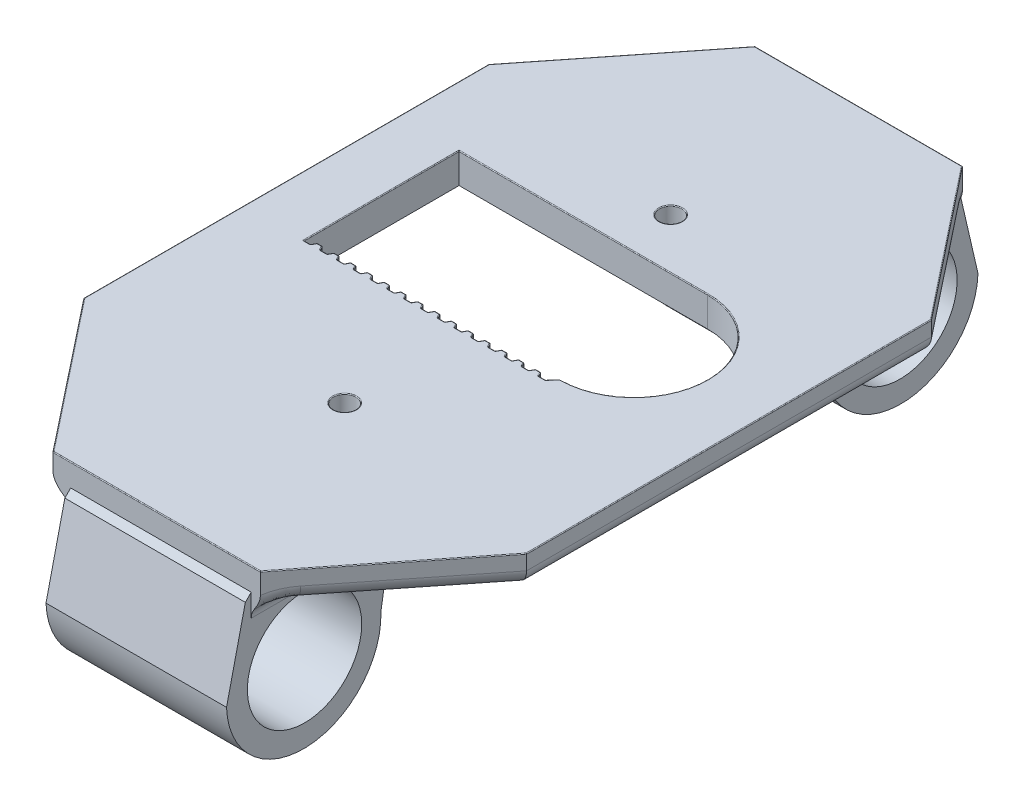
SolidWorks part; units mm, degrees
ref_plane "Front Plane" through (0, 0, 0) normal (0, 0, 1) x (1, 0, 0)
ref_plane "Top Plane" through (0, 0, 0) normal (0, 1, 0) x (1, 0, 0)
ref_plane "Right Plane" through (0, 0, 0) normal (1, 0, 0) x (0, 0, -1)
sketch "Sketch1" plane through (0, 0, 0) normal (0, 1, 0) x (1, 0, 0)
  line L0 (7.0479, -4.6463) -> (7.0479, 14.9632) construction
  line L1 (-25.9915, 14.9632) -> (-25.9915, -5.6662)
  line L2 (-25.9915, 4.6485) -> (16.8527, 5.1585) construction
  line L3 (-117.0016, -46.4316) -> (-117.0016, 46.6684) construction
  line L4 (-117.0016, 46.6684) -> (67.0292, 46.6684) construction
  line L5 (60, -47.6441) -> (-60, 47.3559) construction
  line L6 (60, 47.3559) -> (-60, -47.6441) construction
  line L7 (-25.9915, 14.9632) -> (7.0479, 14.9632)
  line L8 (-20.2659, -5.09) -> (-19.7122, -5.09)
  line L9 (-19.6107, -5.1507) -> (-19.3663, -5.6055)
  line L10 (-19.2648, -5.6662) -> (-18.4807, -5.6662)
  line L11 (-18.0333, -5.09) -> (-17.4796, -5.09)
  line L12 (-18.1348, -5.1507) -> (-18.3791, -5.6055)
  line L13 (-17.3781, -5.1507) -> (-17.1338, -5.6055)
  line L14 (-17.0322, -5.6662) -> (-16.2481, -5.6662)
  line L15 (-15.8007, -5.09) -> (-15.247, -5.09)
  line L16 (-15.9022, -5.1507) -> (-16.1466, -5.6055)
  line L17 (-15.1455, -5.1507) -> (-14.9012, -5.6055)
  line L18 (-14.7996, -5.6662) -> (-14.0155, -5.6662)
  line L19 (-13.5681, -5.09) -> (-13.0144, -5.09)
  line L20 (-13.6696, -5.1507) -> (-13.914, -5.6055)
  line L21 (-12.9129, -5.1507) -> (-12.6686, -5.6055)
  line L22 (-12.5671, -5.6662) -> (-11.7829, -5.6662)
  line L23 (-11.3355, -5.09) -> (-10.7819, -5.09)
  line L24 (-11.4371, -5.1507) -> (-11.6814, -5.6055)
  line L25 (-10.6803, -5.1507) -> (-10.436, -5.6055)
  line L26 (-10.3345, -5.6662) -> (-9.5503, -5.6662)
  line L27 (-9.1029, -5.09) -> (-8.5493, -5.09)
  line L28 (-9.2045, -5.1507) -> (-9.4488, -5.6055)
  line L29 (-8.4478, -5.1507) -> (-8.2034, -5.6055)
  line L30 (-8.1019, -5.6662) -> (-7.3177, -5.6662)
  line L31 (-6.8704, -5.09) -> (-6.3167, -5.09)
  line L32 (-6.9719, -5.1507) -> (-7.2162, -5.6055)
  line L33 (-6.2152, -5.1507) -> (-5.9708, -5.6055)
  line L34 (-5.8693, -5.6662) -> (-5.0852, -5.6662)
  line L35 (-4.6378, -5.09) -> (-4.0841, -5.09)
  line L36 (-4.7393, -5.1507) -> (-4.9836, -5.6055)
  line L37 (-3.9826, -5.1507) -> (-3.7383, -5.6055)
  line L38 (-3.6367, -5.6662) -> (-2.8526, -5.6662)
  line L39 (-2.5067, -5.1507) -> (-2.751, -5.6055)
  line L40 (-2.4052, -5.09) -> (-1.8515, -5.09)
  line L41 (-1.75, -5.1507) -> (-1.5057, -5.6055)
  line L42 (-1.4041, -5.6662) -> (-0.62, -5.6662)
  line L43 (-0.1726, -5.09) -> (0.3811, -5.09)
  line L44 (-0.2741, -5.1507) -> (-0.5185, -5.6055)
  line L45 (0.4826, -5.1507) -> (0.7269, -5.6055)
  line L46 (0.8284, -5.6662) -> (1.6126, -5.6662)
  line L47 (2.06, -5.09) -> (2.6136, -5.09)
  line L48 (1.9585, -5.1507) -> (1.7141, -5.6055)
  line L49 (2.7152, -5.1507) -> (2.9595, -5.6055)
  line L50 (3.061, -5.6662) -> (3.8452, -5.6662)
  line L51 (4.2926, -5.09) -> (4.8462, -5.09)
  line L52 (4.191, -5.1507) -> (3.9467, -5.6055)
  line L53 (4.9478, -5.1507) -> (5.1921, -5.6055)
  line L54 (5.2936, -5.6662) -> (6.0778, -5.6662)
  line L55 (-4.5704, -46.6684) -> (-4.5704, -21.6684) construction
  line L56 (7.0479, -4.6463) -> (6.1793, -5.6055)
  line L57 (-33.9974, 26.9146) -> (-33.9974, 0)
  line L58 (-33.9974, 26.9146) -> (-18.359, 46.6684)
  line L59 (16.8527, 5.1585) -> (-4.5704, 4.9035) construction
  line L60 (59.555, 0.1184) -> (59.555, 109.8543) construction
  line L61 (-4.5704, 4.9035) -> (-4.5704, 35.9939) construction
  line L62 (-18.359, 46.6684) -> (9.2182, 46.6684)
  line L63 (0, 0) -> (-89.2784, 0) construction
  line L64 (-4.5704, 8.3581) -> (-4.5704, -66.3474) construction
  line L65 (-18.359, -46.6684) -> (9.2182, -46.6684)
  line L66 (24.8566, 26.9146) -> (9.2182, 46.6684)
  line L67 (-33.9974, -26.9146) -> (-18.359, -46.6684)
  line L68 (-33.9974, -26.9146) -> (-33.9974, 0)
  line L69 (24.8566, 26.9146) -> (24.8566, 0)
  line L70 (24.8566, -26.9146) -> (24.8566, 0)
  line L71 (24.8566, -26.9146) -> (9.2182, -46.6684)
  line L72 (-4.5704, 46.6684) -> (-4.5704, 21.6684) construction
  line L104 (-25.9915, -5.6662) -> (-25.1784, -5.6662)
  line L105 (-24.731, -5.09) -> (-24.1774, -5.09)
  line L106 (-24.8326, -5.1507) -> (-25.0769, -5.6055)
  line L107 (-24.0758, -5.1507) -> (-23.8315, -5.6055)
  line L108 (-23.73, -5.6662) -> (-22.9458, -5.6662)
  line L109 (-22.4984, -5.09) -> (-21.9448, -5.09)
  line L110 (-22.6, -5.1507) -> (-22.8443, -5.6055)
  line L111 (-21.8433, -5.1507) -> (-21.5989, -5.6055)
  line L112 (-21.4974, -5.6662) -> (-20.7132, -5.6662)
  line L114 (-20.3674, -5.1507) -> (-20.6117, -5.6055)
  circle A0 centre (-4.5704, -21.6684) radius 1.5
  arc A1 (-19.3663, -5.6055) -> (-19.2648, -5.6662) centre (-19.2648, -5.551) ccw
  circle A2 centre (-4.5704, 21.6684) radius 1.5
  arc A7 (-19.6107, -5.1507) -> (-19.7122, -5.09) centre (-19.7122, -5.2052) ccw
  arc A8 (-17.1338, -5.6055) -> (-17.0322, -5.6662) centre (-17.0322, -5.551) ccw
  arc A9 (-18.0333, -5.09) -> (-18.1348, -5.1507) centre (-18.0333, -5.2052) ccw
  arc A10 (-18.4807, -5.6662) -> (-18.3791, -5.6055) centre (-18.4807, -5.551) ccw
  arc A11 (-17.3781, -5.1507) -> (-17.4796, -5.09) centre (-17.4796, -5.2052) ccw
  arc A32 (-23.8315, -5.6055) -> (-23.73, -5.6662) centre (-23.73, -5.551) ccw
  arc A33 (-24.731, -5.09) -> (-24.8326, -5.1507) centre (-24.731, -5.2052) ccw
  arc A34 (-25.1784, -5.6662) -> (-25.0769, -5.6055) centre (-25.1784, -5.551) ccw
  arc A35 (-24.0758, -5.1507) -> (-24.1774, -5.09) centre (-24.1774, -5.2052) ccw
  arc A36 (-21.5989, -5.6055) -> (-21.4974, -5.6662) centre (-21.4974, -5.551) ccw
  arc A37 (-22.4984, -5.09) -> (-22.6, -5.1507) centre (-22.4984, -5.2052) ccw
  arc A38 (-22.9458, -5.6662) -> (-22.8443, -5.6055) centre (-22.9458, -5.551) ccw
  arc A39 (-21.8433, -5.1507) -> (-21.9448, -5.09) centre (-21.9448, -5.2052) ccw
  arc A40 (-14.9012, -5.6055) -> (-14.7996, -5.6662) centre (-14.7996, -5.551) ccw
  arc A41 (-20.2659, -5.09) -> (-20.3674, -5.1507) centre (-20.2659, -5.2052) ccw
  arc A42 (-20.7132, -5.6662) -> (-20.6117, -5.6055) centre (-20.7132, -5.551) ccw
  arc A43 (-15.8007, -5.09) -> (-15.9022, -5.1507) centre (-15.8007, -5.2052) ccw
  arc A44 (-16.2481, -5.6662) -> (-16.1466, -5.6055) centre (-16.2481, -5.551) ccw
  arc A45 (-15.1455, -5.1507) -> (-15.247, -5.09) centre (-15.247, -5.2052) ccw
  arc A46 (-12.6686, -5.6055) -> (-12.5671, -5.6662) centre (-12.5671, -5.551) ccw
  arc A47 (-13.5681, -5.09) -> (-13.6696, -5.1507) centre (-13.5681, -5.2052) ccw
  arc A48 (-14.0155, -5.6662) -> (-13.914, -5.6055) centre (-14.0155, -5.551) ccw
  arc A49 (-12.9129, -5.1507) -> (-13.0144, -5.09) centre (-13.0144, -5.2052) ccw
  arc A50 (-10.436, -5.6055) -> (-10.3345, -5.6662) centre (-10.3345, -5.551) ccw
  arc A51 (-11.3355, -5.09) -> (-11.4371, -5.1507) centre (-11.3355, -5.2052) ccw
  arc A52 (-11.7829, -5.6662) -> (-11.6814, -5.6055) centre (-11.7829, -5.551) ccw
  arc A53 (-10.6803, -5.1507) -> (-10.7819, -5.09) centre (-10.7819, -5.2052) ccw
  arc A54 (-8.2034, -5.6055) -> (-8.1019, -5.6662) centre (-8.1019, -5.551) ccw
  arc A55 (-9.1029, -5.09) -> (-9.2045, -5.1507) centre (-9.1029, -5.2052) ccw
  arc A56 (-9.5503, -5.6662) -> (-9.4488, -5.6055) centre (-9.5503, -5.551) ccw
  arc A57 (-8.4478, -5.1507) -> (-8.5493, -5.09) centre (-8.5493, -5.2052) ccw
  arc A58 (-5.9708, -5.6055) -> (-5.8693, -5.6662) centre (-5.8693, -5.551) ccw
  arc A59 (-6.8704, -5.09) -> (-6.9719, -5.1507) centre (-6.8704, -5.2052) ccw
  arc A60 (-7.3177, -5.6662) -> (-7.2162, -5.6055) centre (-7.3177, -5.551) ccw
  arc A61 (-6.2152, -5.1507) -> (-6.3167, -5.09) centre (-6.3167, -5.2052) ccw
  arc A62 (-3.7383, -5.6055) -> (-3.6367, -5.6662) centre (-3.6367, -5.551) ccw
  arc A63 (-4.6378, -5.09) -> (-4.7393, -5.1507) centre (-4.6378, -5.2052) ccw
  arc A64 (-5.0852, -5.6662) -> (-4.9836, -5.6055) centre (-5.0852, -5.551) ccw
  arc A65 (-3.9826, -5.1507) -> (-4.0841, -5.09) centre (-4.0841, -5.2052) ccw
  arc A66 (-2.4052, -5.09) -> (-2.5067, -5.1507) centre (-2.4052, -5.2052) ccw
  arc A67 (-2.8526, -5.6662) -> (-2.751, -5.6055) centre (-2.8526, -5.551) ccw
  arc A68 (-1.5057, -5.6055) -> (-1.4041, -5.6662) centre (-1.4041, -5.551) ccw
  arc A69 (-1.75, -5.1507) -> (-1.8515, -5.09) centre (-1.8515, -5.2052) ccw
  arc A70 (0.7269, -5.6055) -> (0.8284, -5.6662) centre (0.8284, -5.551) ccw
  arc A71 (-0.1726, -5.09) -> (-0.2741, -5.1507) centre (-0.1726, -5.2052) ccw
  arc A72 (-0.62, -5.6662) -> (-0.5185, -5.6055) centre (-0.62, -5.551) ccw
  arc A73 (0.4826, -5.1507) -> (0.3811, -5.09) centre (0.3811, -5.2052) ccw
  arc A74 (2.9595, -5.6055) -> (3.061, -5.6662) centre (3.061, -5.551) ccw
  arc A75 (2.06, -5.09) -> (1.9585, -5.1507) centre (2.06, -5.2052) ccw
  arc A76 (1.6126, -5.6662) -> (1.7141, -5.6055) centre (1.6126, -5.551) ccw
  arc A77 (2.7152, -5.1507) -> (2.6136, -5.09) centre (2.6136, -5.2052) ccw
  arc A78 (5.1921, -5.6055) -> (5.2936, -5.6662) centre (5.2936, -5.551) ccw
  arc A79 (4.2926, -5.09) -> (4.191, -5.1507) centre (4.2926, -5.2052) ccw
  arc A80 (3.8452, -5.6662) -> (3.9467, -5.6055) centre (3.8452, -5.551) ccw
  arc A81 (4.9478, -5.1507) -> (4.8462, -5.09) centre (4.8462, -5.2052) ccw
  arc A82 (7.0479, 14.9632) -> (7.0479, -4.6463) centre (7.0479, 5.1585) cw
  arc A84 (6.0778, -5.6662) -> (6.1793, -5.6055) centre (6.0778, -5.551) ccw
  point P0 (-3.625, 9.7355)
  point P71 (-26.1782, -36.7915)
  point P109 (17.0374, -36.7915)
  point P110 (-4.5704, 46.6684)
  point P114 (-4.5704, -46.6684)
extrude "Boss-Extrude1" add sketch "Sketch1" along normal blind 4
ref_plane "Plane1" through (2.0085, 0, 0) normal (1, 0, 0) x (0, 0, -1)
sketch "Sketch3" plane through (2.0085, 0, 0) normal (1, 0, 0) x (0, 0, -1)
  line L1 (-29.4309, -9.8861) -> (-27.844, 0)
  line L2 (-49.9539, -10.6185) -> (-47.5, 0)
  line L3 (-47.5, 0) -> (-27.844, 0)
  line L4 (47.5, 0) -> (27.844, 0)
  line L5 (0, 0) -> (0, -31.5545) construction
  line L7 (49.9539, -10.6185) -> (47.5, 0)
  line L8 (29.4309, -9.8861) -> (27.844, 0)
  circle A0 centre (-39.581, -10) radius 7.6
  arc A1 (-49.9539, -10.6185) -> (-29.4309, -9.8861) centre (-39.6924, -10.2523) ccw
  arc A2 (49.9539, -10.6185) -> (29.4309, -9.8861) centre (39.6924, -10.2523) cw
  circle A3 centre (39.581, -10) radius 7.6
extrude "Boss-Extrude2" add sketch "Sketch3" along normal blind 6 and the other way blind 18
chamfer "Chamfer1" distance 1 angle 45 2 edges at (-3.9915, 0, 46.6684) (-3.9915, 0, -46.6684)
fillet "Fillet5" radius 2 6 edges at (-15.9915, 0, 37.2562) (-15.9915, 0, -37.2562) (-3.9915, 0, -27.844) (8.0085, 0, 37.2562) (-3.9915, 0, 27.844) (8.0085, 0, -37.2562)
fillet "Fillet6" radius 2 8 edges at (9.605, -0.0411, -46.1797) (9.605, -0.0411, 46.1797) (17.4325, 0, -36.2923) (-26.1782, 0, 36.7915) (-33.9974, 0, 0) (-26.1782, 0, -36.7915) (24.8566, 0, 0) (17.4325, 0, 36.2923)
fillet "Fillet9" radius 0.1 128 edges at (-25.585, 4, 5.6662) (-25.1193, 4, 5.6499) (-24.9547, 4, 5.3781) (-24.7902, 4, 5.1063) (-24.4542, 4, 5.09) (-24.1182, 4, 5.1063) (-23.9537, 4, 5.3781) (-23.7891, 4, 5.6499) (-23.3379, 4, 5.6662) (-22.8867, 4, 5.6499) (-22.7221, 4, 5.3781) (-22.5576, 4, 5.1063) (-22.2216, 4, 5.09) (-21.8856, 4, 5.1063) (-21.7211, 4, 5.3781) (-21.5565, 4, 5.6499) (-21.1053, 4, 5.6662) (-20.6541, 4, 5.6499) (-20.4896, 4, 5.3781) (-20.325, 4, 5.1063) (-19.989, 4, 5.09) (-19.6531, 4, 5.1063) (-19.4885, 4, 5.3781) (-19.324, 4, 5.6499) (-18.8727, 4, 5.6662) (-18.4215, 4, 5.6499) (-18.257, 4, 5.3781) (-18.0924, 4, 5.1063) (-17.7564, 4, 5.09) (-17.4205, 4, 5.1063) (-17.2559, 4, 5.3781) (-17.0914, 4, 5.6499) (-16.6402, 4, 5.6662) (-16.1889, 4, 5.6499) (-16.0244, 4, 5.3781) (-15.8598, 4, 5.1063) (-15.5239, 4, 5.09) (-15.1879, 4, 5.1063) (-15.0233, 4, 5.3781) (-14.8588, 4, 5.6499) (-14.4076, 4, 5.6662) (-13.9563, 4, 5.6499) (-13.7918, 4, 5.3781) (-13.6273, 4, 5.1063) (-13.2913, 4, 5.09) (-12.9553, 4, 5.1063) (-12.7908, 4, 5.3781) (-12.6262, 4, 5.6499) (-12.175, 4, 5.6662) (-11.7238, 4, 5.6499) (-11.5592, 4, 5.3781) (-11.3947, 4, 5.1063) (-11.0587, 4, 5.09) (-10.7227, 4, 5.1063) (-10.5582, 4, 5.3781) (-10.3936, 4, 5.6499) (-9.9424, 4, 5.6662) (-9.4912, 4, 5.6499) (-9.3266, 4, 5.3781) (-9.1621, 4, 5.1063) (-8.8261, 4, 5.09) (-8.4901, 4, 5.1063) (-8.3256, 4, 5.3781) (-8.161, 4, 5.6499) (-7.7098, 4, 5.6662) (-7.2586, 4, 5.6499) (-7.094, 4, 5.3781) (-6.9295, 4, 5.1063) (-6.5935, 4, 5.09) (-6.2575, 4, 5.1063) (-6.093, 4, 5.3781) (-5.9285, 4, 5.6499) (-5.4772, 4, 5.6662) (-5.026, 4, 5.6499) (-4.8615, 4, 5.3781) (-4.6969, 4, 5.1063) (-4.3609, 4, 5.09) (-4.025, 4, 5.1063) (-3.8604, 4, 5.3781) (-3.6959, 4, 5.6499) (-3.2446, 4, 5.6662) (-2.7934, 4, 5.6499) (-2.6289, 4, 5.3781) (-2.4643, 4, 5.1063) (-2.1284, 4, 5.09) (-1.7924, 4, 5.1063) (-1.6278, 4, 5.3781) (-1.4633, 4, 5.6499) (-1.0121, 4, 5.6662) (-0.5608, 4, 5.6499) (-0.3963, 4, 5.3781) (-0.2317, 4, 5.1063) (0.1042, 4, 5.09) (0.4402, 4, 5.1063) (0.6047, 4, 5.3781) (0.7693, 4, 5.6499) (1.2205, 4, 5.6662) (1.6717, 4, 5.6499) (1.8363, 4, 5.3781) (2.0008, 4, 5.1063) (2.3368, 4, 5.09) (2.6728, 4, 5.1063) (2.8373, 4, 5.3781) (3.0019, 4, 5.6499) (3.4531, 4, 5.6662) (3.9043, 4, 5.6499) (4.0689, 4, 5.3781) (4.2334, 4, 5.1063) (4.5694, 4, 5.09) (4.9054, 4, 5.1063) (5.0699, 4, 5.3781) (5.2345, 4, 5.6499) (5.6857, 4, 5.6662) (6.1369, 4, 5.6499) (6.6136, 4, 5.1259) (16.8527, 4, -5.1585) (-9.4718, 4, -14.9632) (-25.9915, 4, -4.6485) (-4.5704, 4, -46.6684) (17.0374, 4, -36.7915) (24.8566, 4, 0) (17.0374, 4, 36.7915) (-4.5704, 4, 46.6684) (-26.1782, 4, 36.7915) (-33.9974, 4, 0) (-26.1782, 4, -36.7915) (-4.5704, 4, 23.1684) (-4.5704, 4, -20.1684)
